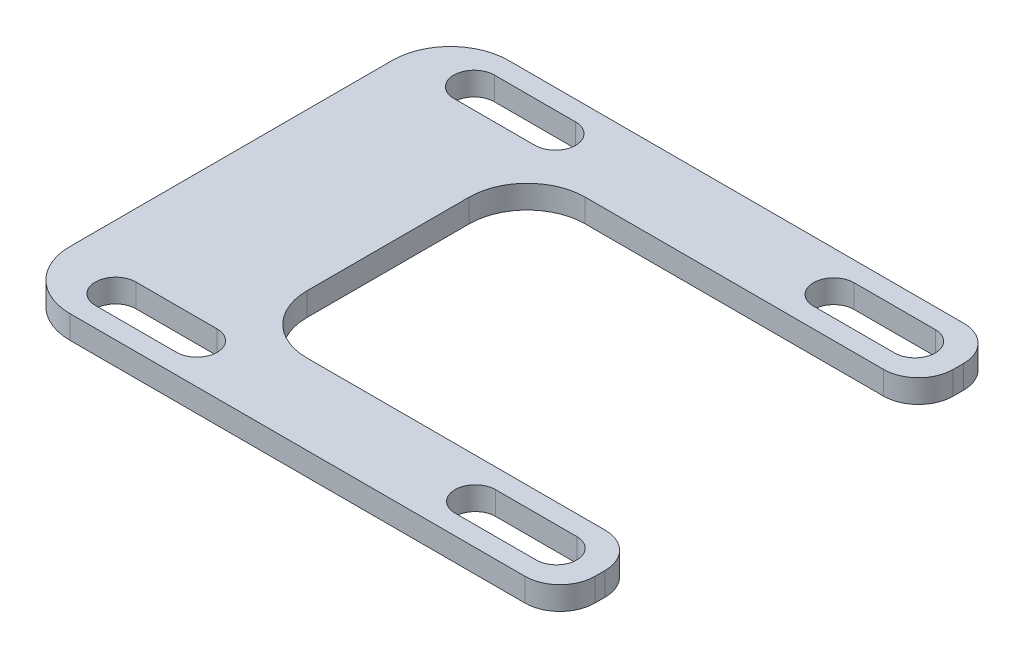
SolidWorks part; units mm, degrees
ref_plane "Front Plane" through (0, 0, 0) normal (0, 0, 1) x (1, 0, 0)
ref_plane "Top Plane" through (0, 0, 0) normal (0, 1, 0) x (1, 0, 0)
ref_plane "Right Plane" through (0, 0, 0) normal (1, 0, 0) x (0, 0, -1)
sketch "Sketch1" plane through (0, 0, 0) normal (0, 1, 0) x (1, 0, 0)
  line L0 (47.2433, 30.9) -> (47.2433, 37.8)
  line L1 (47.2433, 6.9) -> (13.5188, 6.9)
  line L3 (47.2433, 30.9) -> (13.5188, 30.9)
  line L4 (13.5188, 6.9) -> (13.5188, 30.9)
  line L5 (5.4933, 34.35) -> (12.4933, 34.35) construction
  line L6 (5.4933, 36.1) -> (12.4933, 36.1)
  line L7 (47.2433, 0) -> (0, 0)
  line L9 (47.2433, 37.8) -> (0, 37.8)
  line L10 (0, 0) -> (0, 37.8)
  line L11 (5.4933, 32.6) -> (12.4933, 32.6)
  line L12 (36.4933, 34.35) -> (43.4933, 34.35) construction
  line L13 (47.2433, 6.9) -> (47.2433, 0)
  line L14 (36.4933, 36.1) -> (43.4933, 36.1)
  line L15 (36.4933, 32.6) -> (43.4933, 32.6)
  line L16 (5.4933, 3.45) -> (12.4933, 3.45) construction
  line L17 (5.4933, 5.2) -> (12.4933, 5.2)
  line L18 (5.4933, 1.7) -> (12.4933, 1.7)
  line L19 (36.4933, 3.45) -> (43.4933, 3.45) construction
  line L20 (36.4933, 5.2) -> (43.4933, 5.2)
  line L21 (36.4933, 1.7) -> (43.4933, 1.7)
  line L22 (8.9933, 34.35) -> (39.9933, 3.45) construction
  line L23 (39.9933, 34.35) -> (8.9933, 3.45) construction
  arc A0 (5.4933, 36.1) -> (5.4933, 32.6) centre (5.4933, 34.35) ccw
  arc A1 (12.4933, 32.6) -> (12.4933, 36.1) centre (12.4933, 34.35) ccw
  arc A2 (36.4933, 36.1) -> (36.4933, 32.6) centre (36.4933, 34.35) ccw
  arc A3 (43.4933, 32.6) -> (43.4933, 36.1) centre (43.4933, 34.35) ccw
  arc A4 (5.4933, 5.2) -> (5.4933, 1.7) centre (5.4933, 3.45) ccw
  arc A5 (12.4933, 1.7) -> (12.4933, 5.2) centre (12.4933, 3.45) ccw
  arc A6 (36.4933, 5.2) -> (36.4933, 1.7) centre (36.4933, 3.45) ccw
  arc A7 (43.4933, 1.7) -> (43.4933, 5.2) centre (43.4933, 3.45) ccw
  point P0 (0, 0)
  point P6 (0, 0)
  point P8 (8.9933, 34.35)
  point P18 (39.9933, 34.35)
  point P25 (8.9933, 3.45)
  point P32 (39.9933, 3.45)
  point P39 (47.2433, 34.35)
  point P40 (47.2433, 3.45)
  point P43 (45.2433, 34.35)
  dimension "D3" = 1.75
  dimension "D1" = 6.9
  dimension "D2" = 7
  dimension "D4" = 38
  dimension "D5" = 2
  dimension "D6" = 30.9
extrude "Boss-Extrude1" add sketch "Sketch1" along normal blind 2
fillet "Fillet1" radius 5 4 edges at (0, 1, -37.8) (0, 1, 0) (13.5188, 1, -6.9) (13.5188, 1, -30.9)
fillet "Fillet2" radius 3 4 edges at (47.2433, 1, -6.9) (47.2433, 1, 0) (47.2433, 1, -30.9) (47.2433, 1, -37.8)
